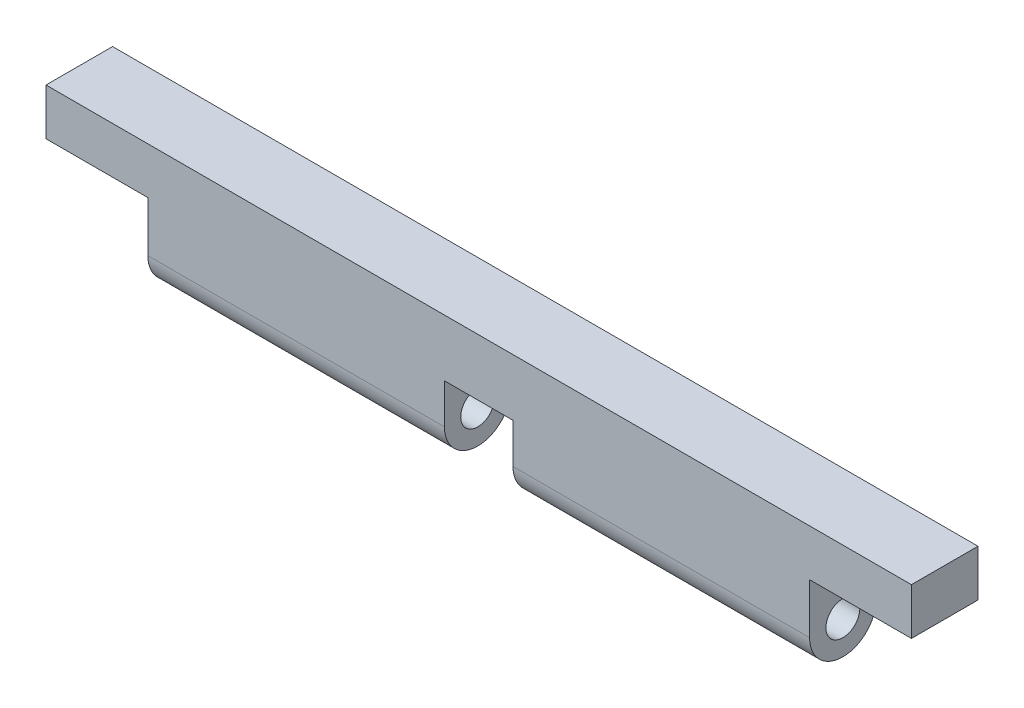
SolidWorks part; units mm, degrees
ref_plane "Front Plane" through (0, 0, 0) normal (0, 0, 1) x (1, 0, 0)
ref_plane "Top Plane" through (0, 0, 0) normal (0, 1, 0) x (1, 0, 0)
ref_plane "Right Plane" through (0, 0, 0) normal (1, 0, 0) x (0, 0, -1)
sketch "Sketch1" plane through (0, 0, 0) normal (0, 0, 1) x (1, 0, 0)
  line L0 (0, -55) -> (0, 55) construction
  line L1 (-56, -11) -> (5.15, -11)
  line L2 (-65, 1.55) -> (-65, 8.55)
  line L3 (-65, 8.55) -> (65, 8.55)
  line L4 (65, 1.55) -> (65, 8.55)
  line L5 (-56, -7.3662) -> (65, 8.55) construction
  line L6 (-65, 8.55) -> (56, -7.3662) construction
  line L7 (-5.15, -11) -> (5.15, -11)
  line L8 (-5.15, -11) -> (-5.15, 0)
  line L9 (-5.15, 0) -> (5.15, 0)
  line L10 (5.15, -11) -> (5.15, 0)
  line L11 (-56, -11) -> (-49.7, -11)
  line L12 (-56, -11) -> (-56, 1.55)
  line L13 (-56, 1.55) -> (-49.7, 1.55)
  line L14 (-49.7, -11) -> (-49.7, 1.55)
  line L15 (56, 1.55) -> (49.7, 1.55)
  line L16 (49.7, -11) -> (49.7, 1.55)
  line L17 (56, -11) -> (49.7, -11)
  line L18 (56, -11) -> (56, 1.55)
  line L19 (49.7, -11) -> (56, -11)
  line L21 (-5.15, -11) -> (5.15, -11)
  line L22 (-56, 1.55) -> (-65, 1.55)
  line L23 (56, 1.55) -> (65, 1.55)
  line L24 (49.7, -11) -> (5.15, -11)
  point P0 (0, 0)
  point P10 (0, 0)
  dimension "D2" = 130
  dimension "D3" = 11
  dimension "D4" = 12.55
  dimension "D5" = 6.3
  dimension "D7" = 49.7
  dimension "D11" = 7
  dimension "D12" = 10.3
extrude "Boss-Extrude1" add sketch "Sketch1" along normal mid plane 10 contours L24 L16 L15 L23 L4 L3 L2 L22 L13 L14 L1 L8 L9 L10
sketch "Sketch2" plane through (-65, 0, 0) normal (-1, 0, 0) x (0, 0, 1)
  line L0 (5, -11) -> (-5, -11) construction
  circle A0 centre (0, -5.95) radius 2.55
  dimension "D1" = 5.1
  dimension "D2" = 5.05
extrude "Cut-Extrude1" cut sketch "Sketch2" against normal through all
fillet "Fillet1" radius 5
